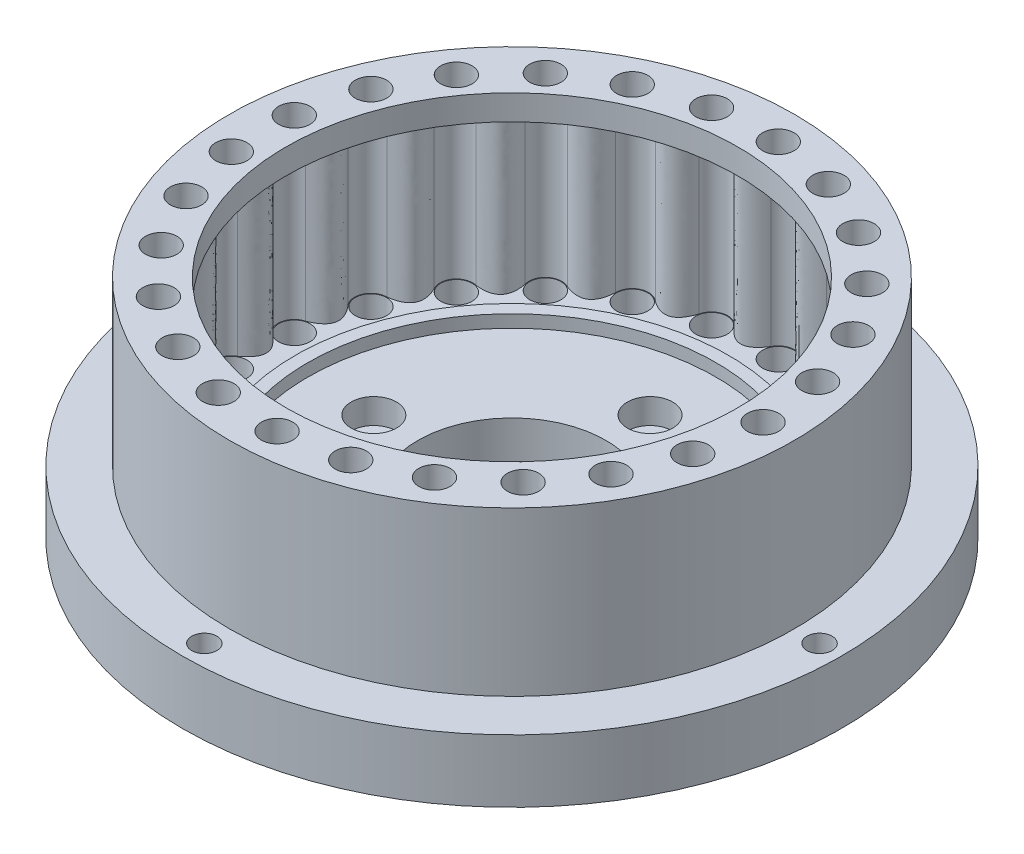
SolidWorks part; units mm, degrees
ref_plane "Front Plane" through (0, 0, 0) normal (0, 0, 1) x (1, 0, 0)
ref_plane "Top Plane" through (0, 0, 0) normal (0, 1, 0) x (1, 0, 0)
ref_plane "Right Plane" through (0, 0, 0) normal (1, 0, 0) x (0, 0, -1)
sketch "Sketch1" plane through (0, 0, 0) normal (0, 1, 0) x (1, 0, 0)
  circle A1 centre (0, 0) radius 45
  circle A2 centre (0, 0) radius 22 construction
  circle A3 centre (0, -22) radius 2
  circle A5 centre (-22, 0) radius 2
  circle A6 centre (0, 22) radius 2
  circle A7 centre (22, 0) radius 2
  point P15 (0, 0)
  dimension "D1" = 90
  dimension "D2" = 44
  dimension "D3" = 4
  dimension "D4" = 4
  dimension "D5" = 90
  dimension "D6" = 22
extrude "Boss-Extrude1" add sketch "Sketch1" along normal blind 6
sketch "Sketch2" plane through (0, 6, 0) normal (0, 1, 0) x (1, 0, 0)
  circle A0 centre (0, 0) radius 22 construction
  circle A1 centre (0, 22) radius 3.61
  circle A2 centre (22, 0) radius 3.61
  circle A3 centre (0, -22) radius 3.61
  circle A4 centre (-22, 0) radius 3.61
  point P14 (0, 0)
  dimension "D1" = 44
  dimension "D2" = 7.22
  dimension "D4" = 22
  dimension "D5" = 90
  dimension "D3" = 4
extrude "Cut-Extrude1" cut sketch "Sketch2" against normal blind 4
sketch "Sketch4" plane through (0, 6, 0) normal (0, 1, 0) x (1, 0, 0)
  circle A0 centre (0, 0) radius 15
  dimension "D1" = 30
extrude "Cut-Extrude2" cut sketch "Sketch4" against normal through all
sketch "Sketch5" plane through (0, 6, 0) normal (0, 1, 0) x (1, 0, 0)
  circle A0 centre (40, 0) radius 2.5
  circle A1 centre (38.7433, -9.9476) radius 2.5
  circle A2 centre (35.0523, -19.2701) radius 2.5
  circle A3 centre (29.1587, -27.3819) radius 2.5
  circle A4 centre (21.4331, -33.7731) radius 2.5
  circle A5 centre (12.3607, -38.0423) radius 2.5
  circle A6 centre (2.5116, -39.9211) radius 2.5
  circle A7 centre (-7.4953, -39.2915) radius 2.5
  circle A8 centre (-17.0312, -36.1931) radius 2.5
  circle A9 centre (-25.497, -30.8205) radius 2.5
  circle A10 centre (-32.3607, -23.5114) radius 2.5
  circle A11 centre (-37.1911, -14.725) radius 2.5
  circle A12 centre (-39.6846, -5.0133) radius 2.5
  circle A13 centre (-39.6846, 5.0133) radius 2.5
  circle A14 centre (-37.1911, 14.725) radius 2.5
  circle A15 centre (-32.3607, 23.5114) radius 2.5
  circle A16 centre (-25.497, 30.8205) radius 2.5
  circle A17 centre (-17.0312, 36.1931) radius 2.5
  circle A18 centre (-7.4953, 39.2915) radius 2.5
  circle A19 centre (2.5116, 39.9211) radius 2.5
  circle A20 centre (12.3607, 38.0423) radius 2.5
  circle A21 centre (21.4331, 33.7731) radius 2.5
  circle A22 centre (29.1587, 27.3819) radius 2.5
  circle A23 centre (35.0523, 19.2701) radius 2.5
  circle A24 centre (38.7433, 9.9476) radius 2.5
  point P53 (0, 0)
  dimension "D2" = 5
  dimension "D1" = 40
  dimension "D3" = 25
extrude "Cut-Extrude3" cut sketch "Sketch5" against normal blind 4
sketch "Sketch6" plane through (0, 6, 0) normal (0, 1, 0) x (1, 0, 0)
  circle A0 centre (0, 0) radius 32.5
  circle A1 centre (0, 0) radius 34.5
  dimension "D1" = 65
  dimension "D2" = 69
extrude "Boss-Extrude2" add sketch "Sketch6" along normal blind 2
sketch "Sketch7" plane through (0, 6, 0) normal (0, 1, 0) x (1, 0, 0)
  line L0 (0, 0) -> (35.0523, -19.2701) construction
  line L1 (0, 0) -> (27.3363, -25.6705) construction
  line L2 (35.0523, -19.2701) -> (34.7909, -21.7565) construction
  line L3 (29.1587, -27.3819) -> (31.4426, -26.365) construction
  line L4 (0, 0) -> (31.5517, -22.9236) construction
  circle A0 centre (35.0523, -19.2701) radius 2.5 construction
  circle A1 centre (38.7433, -9.9476) radius 2.5 construction
  circle A2 centre (40, 0) radius 2.5 construction
  circle A3 centre (38.7433, 9.9476) radius 2.5 construction
  circle A4 centre (35.0523, 19.2701) radius 2.5 construction
  circle A5 centre (29.1587, 27.3819) radius 2.5 construction
  circle A6 centre (21.4331, 33.7731) radius 2.5 construction
  circle A7 centre (12.3607, 38.0423) radius 2.5 construction
  circle A8 centre (2.5116, 39.9211) radius 2.5 construction
  circle A9 centre (-7.4953, 39.2915) radius 2.5 construction
  circle A10 centre (-17.0312, 36.1931) radius 2.5 construction
  circle A11 centre (-25.497, 30.8205) radius 2.5 construction
  circle A12 centre (-32.3607, 23.5114) radius 2.5 construction
  circle A13 centre (-37.1911, 14.725) radius 2.5 construction
  circle A14 centre (-39.6846, 5.0133) radius 2.5 construction
  circle A15 centre (-39.6846, -5.0133) radius 2.5 construction
  circle A16 centre (-37.1911, -14.725) radius 2.5 construction
  circle A17 centre (-32.3607, -23.5114) radius 2.5 construction
  circle A18 centre (-25.497, -30.8205) radius 2.5 construction
  circle A19 centre (-17.0312, -36.1931) radius 2.5 construction
  circle A20 centre (-7.4953, -39.2915) radius 2.5 construction
  circle A21 centre (2.5116, -39.9211) radius 2.5 construction
  circle A22 centre (12.3607, -38.0423) radius 2.5 construction
  circle A23 centre (21.4331, -33.7731) radius 2.5 construction
  circle A24 centre (29.1587, -27.3819) radius 2.5 construction
  arc A25 (34.7909, -21.7565) -> (37.0115, -17.7173) centre (35.0523, -19.2701) ccw construction
  arc A26 (39.1085, -12.4208) -> (40.2548, -7.9563) centre (38.7433, -9.9476) ccw construction
  arc A27 (40.9688, -2.3047) -> (40.9688, 2.3047) centre (40, 0) ccw construction
  arc A28 (40.2548, 7.9563) -> (39.1085, 12.4208) centre (38.7433, 9.9476) ccw construction
  arc A29 (37.0115, 17.7173) -> (34.7909, 21.7565) centre (35.0523, 19.2701) ccw construction
  arc A30 (31.4426, 26.365) -> (28.2873, 29.7251) centre (29.1587, 27.3819) ccw construction
  arc A31 (23.8981, 33.3562) -> (20.0063, 35.826) centre (21.4331, 33.7731) ccw construction
  arc A32 (14.8519, 38.2515) -> (10.4682, 39.6758) centre (12.3607, 38.0423) ccw construction
  arc A33 (4.8726, 40.7432) -> (0.2723, 41.0327) centre (2.5116, 39.9211) ccw construction
  arc A34 (-5.4129, 40.675) -> (-9.9406, 39.8113) centre (-7.4953, 39.2915) ccw construction
  arc A35 (-15.3583, 38.0509) -> (-19.529, 36.0884) centre (-17.0312, 36.1931) ccw construction
  arc A36 (-24.3387, 33.036) -> (-27.8903, 30.098) centre (-25.497, 30.8205) ccw construction
  arc A37 (-31.7898, 25.9454) -> (-34.4991, 22.2163) centre (-32.3607, 23.5114) ccw construction
  arc A38 (-37.2434, 17.2244) -> (-38.9402, 12.9388) centre (-37.1911, 14.725) ccw construction
  arc A39 (-40.3569, 7.4212) -> (-40.9346, 2.8483) centre (-39.6846, 5.0133) ccw construction
  arc A40 (-40.9346, -2.8483) -> (-40.3569, -7.4212) centre (-39.6846, -5.0133) ccw construction
  arc A41 (-38.9402, -12.9388) -> (-37.2434, -17.2244) centre (-37.1911, -14.725) ccw construction
  arc A42 (-34.4991, -22.2163) -> (-31.7898, -25.9454) centre (-32.3607, -23.5114) ccw construction
  arc A43 (-27.8903, -30.098) -> (-24.3387, -33.036) centre (-25.497, -30.8205) ccw construction
  arc A44 (-19.529, -36.0884) -> (-15.3583, -38.0509) centre (-17.0312, -36.1931) ccw construction
  arc A45 (-9.9406, -39.8113) -> (-5.4129, -40.675) centre (-7.4953, -39.2915) ccw construction
  arc A46 (0.2723, -41.0327) -> (4.8726, -40.7432) centre (2.5116, -39.9211) ccw construction
  arc A47 (10.4682, -39.6758) -> (14.8519, -38.2515) centre (12.3607, -38.0423) ccw construction
  arc A48 (20.0063, -35.826) -> (23.8981, -33.3562) centre (21.4331, -33.7731) ccw construction
  arc A49 (28.2873, -29.7251) -> (31.4426, -26.365) centre (29.1587, -27.3819) ccw construction
  arc A51 (33.4936, -21.8672) -> (35.0523, -19.2701) centre (0, 0) ccw construction
  arc A53 (23.9272, -32.0545) -> (27.0032, -29.5098) centre (0, 0) ccw construction
  arc A54 (15.2038, -36.9979) -> (18.8161, -35.2981) centre (0, 0) ccw construction
  arc A55 (9.9601, -38.7401) -> (14.713, -37.1958) centre (0, 0) ccw construction
  arc A56 (5.5252, -39.6166) -> (9.4467, -38.8685) centre (0, 0) ccw construction
  arc A57 (-5.0261, -39.683) -> (5.0006, -39.6862) centre (0, 0) ccw construction
  arc A58 (-14.7369, -37.1863) -> (-10.4469, -38.6117) centre (0, 0) ccw construction
  arc A59 (-23.0917, -32.6615) -> (-22.9047, -32.7929) centre (0, 0) ccw construction
  arc A60 (-30.4888, -25.8927) -> (-27.756, -28.8029) centre (0, 0) ccw construction
  arc A61 (-35.9702, -17.4969) -> (-34.047, -20.9953) centre (0, 0) ccw construction
  arc A62 (-39.1915, -8.0018) -> (-38.1986, -11.8686) centre (0, 0) ccw construction
  arc A63 (-39.9502, 1.9961) -> (-39.9502, -1.9961) centre (0, 0) ccw construction
  arc A64 (-38.1986, 11.8686) -> (-39.1915, 8.0018) centre (0, 0) ccw construction
  arc A65 (-36.1986, 17.0195) -> (-38.0383, 12.3729) centre (0, 0) ccw construction
  arc A66 (-34.047, 20.9953) -> (-35.9702, 17.4969) centre (0, 0) ccw construction
  arc A67 (-27.756, 28.8029) -> (-30.4888, 25.8927) centre (0, 0) ccw construction
  arc A68 (-19.2589, 35.0585) -> (-23.0917, 32.6615) centre (0, 0) ccw construction
  arc A69 (-9.9351, 38.7465) -> (-14.7369, 37.1863) centre (0, 0) ccw construction
  arc A70 (-0.5163, 39.9967) -> (-5.0261, 39.683) centre (0, 0) ccw construction
  arc A71 (9.4467, 38.8685) -> (0.0129, 40) centre (0, 0) ccw construction
  arc A72 (18.8161, 35.2981) -> (15.2038, 36.9979) centre (0, 0) ccw construction
  arc A73 (27.0032, 29.5098) -> (23.9272, 32.0545) centre (0, 0) ccw construction
  arc A74 (33.4936, 21.8672) -> (30.8123, 25.5069) centre (0, 0) ccw construction
  arc A75 (37.8795, 12.8507) -> (36.4099, 16.5626) centre (0, 0) ccw construction
  arc A76 (39.8853, 3.0267) -> (39.2891, 7.5079) centre (0, 0) ccw construction
  arc A77 (39.385, -6.9875) -> (39.9219, -2.4988) centre (0, 0) ccw construction
  arc A78 (36.1876, -17.0428) -> (37.8795, -12.8507) centre (0, 0) ccw construction
  circle A79 centre (0, 0) radius 45
  arc A80 (34.7861, -21.8565) -> (37.0934, -17.6596) centre (35.0523, -19.2701) ccw
  arc A81 (39.1287, -12.5189) -> (40.3198, -7.88) centre (38.7433, -9.9476) ccw
  arc A82 (41.0127, -2.3947) -> (41.0127, 2.3947) centre (40, 0) ccw
  arc A83 (40.3198, 7.88) -> (39.1287, 12.5189) centre (38.7433, 9.9476) ccw
  arc A84 (37.0934, 17.6596) -> (34.7861, 21.8565) centre (35.0523, 19.2701) ccw
  arc A85 (31.5362, 26.3295) -> (28.2577, 29.8208) centre (29.1587, 27.3819) ccw
  arc A86 (23.9976, 33.3451) -> (19.9538, 35.9113) centre (21.4331, 33.7731) ccw
  arc A87 (14.9511, 38.2654) -> (10.3962, 39.7454) centre (12.3607, 38.0423) ccw
  arc A88 (4.9651, 40.7814) -> (0.1853, 41.0822) centre (2.5116, 39.9211) ccw
  arc A89 (-5.3328, 40.735) -> (-10.0373, 39.8376) centre (-7.4953, 39.2915) ccw
  arc A90 (-15.2956, 38.129) -> (-19.6291, 36.0898) centre (-17.0312, 36.1931) ccw
  arc A91 (-24.2974, 33.1273) -> (-27.9876, 30.0744) centre (-25.497, 30.8205) ccw
  arc A92 (-31.7724, 26.044) -> (-34.5875, 22.1694) centre (-32.3607, 23.5114) ccw
  arc A93 (-37.2511, 17.3243) -> (-39.0142, 12.8713) centre (-37.1911, 14.725) ccw
  arc A94 (-40.3892, 7.516) -> (-40.9895, 2.7645) centre (-39.6846, 5.0133) ccw
  arc A95 (-40.9895, -2.7645) -> (-40.3892, -7.516) centre (-39.6846, -5.0133) ccw
  arc A96 (-39.0142, -12.8713) -> (-37.2511, -17.3243) centre (-37.1911, -14.725) ccw
  arc A97 (-34.5875, -22.1694) -> (-31.7724, -26.044) centre (-32.3607, -23.5114) ccw
  arc A98 (-27.9876, -30.0744) -> (-24.2974, -33.1273) centre (-25.497, -30.8205) ccw
  arc A99 (-19.6291, -36.0898) -> (-15.2956, -38.129) centre (-17.0312, -36.1931) ccw
  arc A100 (-10.0373, -39.8376) -> (-5.3328, -40.735) centre (-7.4953, -39.2915) ccw
  arc A101 (0.1853, -41.0822) -> (4.9651, -40.7814) centre (2.5116, -39.9211) ccw
  arc A102 (10.3962, -39.7454) -> (14.9511, -38.2654) centre (12.3607, -38.0423) ccw
  arc A103 (19.9538, -35.9113) -> (23.9976, -33.3451) centre (21.4331, -33.7731) ccw
  arc A104 (28.2577, -29.8208) -> (31.5362, -26.3295) centre (29.1587, -27.3819) ccw
  spline S0 degree 2 poles (34.7909, -21.7565) (29.9865, -21.7865) (31.4426, -26.365) knots 0 0 0 1 1 1 construction
  spline S1 degree 2 poles (28.2873, -29.7251) (23.6264, -28.5594) (23.8981, -33.3562) knots 0 0 0 1 1 1 construction
  spline S2 degree 2 poles (20.0063, -35.826) (15.7817, -33.5378) (14.8519, -38.2515) knots 0 0 0 1 1 1 construction
  spline S3 degree 2 poles (10.4682, -39.6758) (6.9454, -36.4089) (4.8726, -40.7432) knots 0 0 0 1 1 1 construction
  spline S4 degree 2 poles (0.2723, -41.0327) (-2.3274, -36.9923) (-5.4129, -40.675) knots 0 0 0 1 1 1 construction
  spline S5 degree 2 poles (-9.9406, -39.8113) (-11.4538, -35.2513) (-15.3583, -38.0509) knots 0 0 0 1 1 1 construction
  spline S6 degree 2 poles (-19.529, -36.0884) (-19.8606, -31.2954) (-24.3387, -33.036) knots 0 0 0 1 1 1 construction
  spline S7 degree 2 poles (-27.8903, -30.098) (-27.0195, -25.373) (-31.7898, -25.9454) knots 0 0 0 1 1 1 construction
  spline S8 degree 2 poles (-34.4991, -22.2163) (-32.4807, -17.8564) (-37.2434, -17.2244) knots 0 0 0 1 1 1 construction
  spline S9 degree 2 poles (-38.9402, -12.9388) (-35.9009, -9.2178) (-40.3569, -7.4212) knots 0 0 0 1 1 1 construction
  spline S10 degree 2 poles (-40.9346, -2.8483) (-37.0654, 0) (-40.9346, 2.8483) knots 0 0 0 1 1 1 construction
  spline S11 degree 2 poles (-40.3569, 7.4212) (-35.9009, 9.2178) (-38.9402, 12.9388) knots 0 0 0 1 1 1 construction
  spline S12 degree 2 poles (-37.2434, 17.2244) (-32.4807, 17.8564) (-34.4991, 22.2163) knots 0 0 0 1 1 1 construction
  spline S13 degree 2 poles (-31.7898, 25.9454) (-27.0195, 25.373) (-27.8903, 30.098) knots 0 0 0 1 1 1 construction
  spline S14 degree 2 poles (-24.3387, 33.036) (-19.8606, 31.2954) (-19.529, 36.0884) knots 0 0 0 1 1 1 construction
  spline S15 degree 2 poles (-15.3583, 38.0509) (-11.4538, 35.2513) (-9.9406, 39.8113) knots 0 0 0 1 1 1 construction
  spline S16 degree 2 poles (-5.4129, 40.675) (-2.3274, 36.9923) (0.2723, 41.0327) knots 0 0 0 1 1 1 construction
  spline S17 degree 2 poles (4.8726, 40.7432) (6.9454, 36.4089) (10.4682, 39.6758) knots 0 0 0 1 1 1 construction
  spline S18 degree 2 poles (14.8519, 38.2515) (15.7817, 33.5378) (20.0063, 35.826) knots 0 0 0 1 1 1 construction
  spline S19 degree 2 poles (23.8981, 33.3562) (23.6264, 28.5594) (28.2873, 29.7251) knots 0 0 0 1 1 1 construction
  spline S20 degree 2 poles (31.4426, 26.365) (29.9865, 21.7865) (34.7909, 21.7565) knots 0 0 0 1 1 1 construction
  spline S21 degree 2 poles (37.0115, 17.7173) (34.4625, 13.6447) (39.1085, 12.4208) knots 0 0 0 1 1 1 construction
  spline S22 degree 2 poles (40.2548, 7.9563) (36.7731, 4.6455) (40.9688, 2.3047) knots 0 0 0 1 1 1 construction
  spline S23 degree 2 poles (40.9688, -2.3047) (36.7731, -4.6455) (40.2548, -7.9563) knots 0 0 0 1 1 1 construction
  spline S24 degree 2 poles (39.1085, -12.4208) (34.4625, -13.6447) (37.0115, -17.7173) knots 0 0 0 1 1 1 construction
  spline S25 degree 1 poles (39.1287, -12.5189) (37.0934, -17.6596) knots 0 0 1 1 construction
  spline S26 degree 1 poles (41.0127, -2.3947) (40.3198, -7.88) knots 0 0 1 1 construction
  spline S27 degree 1 poles (40.3198, 7.88) (41.0127, 2.3947) knots 0 0 1 1 construction
  spline S28 degree 1 poles (37.0934, 17.6596) (39.1287, 12.5189) knots 0 0 1 1 construction
  spline S29 degree 1 poles (31.5362, 26.3295) (34.7861, 21.8565) knots 0 0 1 1 construction
  spline S30 degree 1 poles (23.9976, 33.3451) (28.2577, 29.8208) knots 0 0 1 1 construction
  spline S31 degree 1 poles (14.9511, 38.2654) (19.9538, 35.9113) knots 0 0 1 1 construction
  spline S32 degree 1 poles (4.9651, 40.7814) (10.3962, 39.7454) knots 0 0 1 1 construction
  spline S33 degree 1 poles (-5.3328, 40.735) (0.1853, 41.0822) knots 0 0 1 1 construction
  spline S34 degree 1 poles (-15.2956, 38.129) (-10.0373, 39.8376) knots 0 0 1 1 construction
  spline S35 degree 1 poles (-24.2974, 33.1273) (-19.6291, 36.0898) knots 0 0 1 1 construction
  spline S36 degree 1 poles (-31.7724, 26.044) (-27.9876, 30.0744) knots 0 0 1 1 construction
  spline S37 degree 1 poles (-37.2511, 17.3243) (-34.5875, 22.1694) knots 0 0 1 1 construction
  spline S38 degree 1 poles (-40.3892, 7.516) (-39.0142, 12.8713) knots 0 0 1 1 construction
  spline S39 degree 1 poles (-40.9895, -2.7645) (-40.9895, 2.7645) knots 0 0 1 1 construction
  spline S40 degree 1 poles (-39.0142, -12.8713) (-40.3892, -7.516) knots 0 0 1 1 construction
  spline S41 degree 1 poles (-34.5875, -22.1694) (-37.2511, -17.3243) knots 0 0 1 1 construction
  spline S42 degree 1 poles (-27.9876, -30.0744) (-31.7724, -26.044) knots 0 0 1 1 construction
  spline S43 degree 1 poles (-19.6291, -36.0898) (-24.2974, -33.1273) knots 0 0 1 1 construction
  spline S44 degree 1 poles (-10.0373, -39.8376) (-15.2956, -38.129) knots 0 0 1 1 construction
  spline S45 degree 1 poles (0.1853, -41.0822) (-5.3328, -40.735) knots 0 0 1 1 construction
  spline S46 degree 1 poles (10.3962, -39.7454) (4.9651, -40.7814) knots 0 0 1 1 construction
  spline S47 degree 1 poles (19.9538, -35.9113) (14.9511, -38.2654) knots 0 0 1 1 construction
  spline S48 degree 1 poles (28.2577, -29.8208) (23.9976, -33.3451) knots 0 0 1 1 construction
  spline S49 degree 1 poles (34.7861, -21.8565) (31.5362, -26.3295) knots 0 0 1 1 construction
  spline S50 degree 3 poles (37.0934, -17.6596) (36.9928, -17.4988) (36.7956, -17.161) (36.4917, -16.5417) (36.2467, -15.8185) (36.1759, -15.0518) (36.3187, -14.3796) (36.6748, -13.7918) (37.2512, -13.2814) (37.9249, -12.9219) (38.5703, -12.6785) (38.9453, -12.5673) (39.1287, -12.5189) knots 0.000577 0.000577 0.000577 0.000577 0.063005 0.125433 0.250288 0.375144 0.5 0.624856 0.749712 0.874567 0.936995 0.999423 0.999423 0.999423 0.999423
  spline S51 degree 3 poles (40.3198, -7.88) (40.1824, -7.7493) (39.9074, -7.4711) (39.459, -6.9469) (39.0418, -6.3073) (38.7826, -5.5824) (38.7538, -4.8957) (38.9524, -4.2379) (39.3838, -3.6001) (39.947, -3.0844) (40.5116, -2.6882) (40.8472, -2.4872) (41.0127, -2.3947) knots 0.000577 0.000577 0.000577 0.000577 0.063005 0.125433 0.250288 0.375144 0.5 0.624856 0.749712 0.874567 0.936995 0.999423 0.999423 0.999423 0.999423
  spline S52 degree 3 poles (41.0127, 2.3947) (40.8472, 2.4872) (40.5116, 2.6882) (39.947, 3.0844) (39.3838, 3.6001) (38.9524, 4.2379) (38.7538, 4.8957) (38.7826, 5.5824) (39.0418, 6.3073) (39.459, 6.9469) (39.9074, 7.4711) (40.1824, 7.7493) (40.3198, 7.88) knots 0.000577 0.000577 0.000577 0.000577 0.063005 0.125433 0.250288 0.375144 0.5 0.624856 0.749712 0.874567 0.936995 0.999423 0.999423 0.999423 0.999423
  spline S53 degree 3 poles (39.1287, 12.5189) (38.9453, 12.5673) (38.5703, 12.6785) (37.9249, 12.9219) (37.2512, 13.2814) (36.6748, 13.7918) (36.3187, 14.3796) (36.1759, 15.0518) (36.2467, 15.8185) (36.4917, 16.5417) (36.7956, 17.161) (36.9928, 17.4988) (37.0934, 17.6596) knots 0.000577 0.000577 0.000577 0.000577 0.063005 0.125433 0.250288 0.375144 0.5 0.624856 0.749712 0.874567 0.936995 0.999423 0.999423 0.999423 0.999423
  spline S54 degree 3 poles (34.7861, 21.8565) (34.5964, 21.8578) (34.2055, 21.8722) (33.5199, 21.9475) (32.7779, 22.1281) (32.0927, 22.4791) (31.6016, 22.9599) (31.2961, 23.5755) (31.174, 24.3357) (31.2315, 25.0971) (31.3718, 25.7725) (31.4789, 26.1488) (31.5362, 26.3295) knots 0.000577 0.000577 0.000577 0.000577 0.063005 0.125433 0.250288 0.375144 0.5 0.624856 0.749712 0.874567 0.936995 0.999423 0.999423 0.999423 0.999423
  spline S55 degree 3 poles (28.2577, 29.8208) (28.0737, 29.7749) (27.6915, 29.6917) (27.0087, 29.594) (26.2451, 29.5845) (25.4941, 29.754) (24.8989, 30.0976) (24.4499, 30.6179) (24.1426, 31.3238) (24.0089, 32.0756) (23.9769, 32.7647) (23.987, 33.1557) (23.9976, 33.3451) knots 0.000577 0.000577 0.000577 0.000577 0.063005 0.125433 0.250288 0.375144 0.5 0.624856 0.749712 0.874567 0.936995 0.999423 0.999423 0.999423 0.999423
  spline S56 degree 3 poles (19.9538, 35.9113) (19.787, 35.8211) (19.4375, 35.6454) (18.8004, 35.3811) (18.0632, 35.1819) (17.2936, 35.1594) (16.6317, 35.3442) (16.0674, 35.7364) (15.5942, 36.3437) (15.2777, 37.0387) (15.0754, 37.6981) (14.9879, 38.0794) (14.9511, 38.2654) knots 0.000577 0.000577 0.000577 0.000577 0.063005 0.125433 0.250288 0.375144 0.5 0.624856 0.749712 0.874567 0.936995 0.999423 0.999423 0.999423 0.999423
  spline S57 degree 3 poles (10.3962, 39.7454) (10.257, 39.6165) (9.9622, 39.3595) (9.4108, 38.945) (8.7463, 38.5687) (8.0065, 38.3555) (7.3194, 38.3699) (6.6753, 38.6095) (6.0659, 39.08) (5.5866, 39.6745) (5.2266, 40.2629) (5.0471, 40.6104) (4.9651, 40.7814) knots 0.000577 0.000577 0.000577 0.000577 0.063005 0.125433 0.250288 0.375144 0.5 0.624856 0.749712 0.874567 0.936995 0.999423 0.999423 0.999423 0.999423
  spline S58 degree 3 poles (0.1853, 41.0822) (0.0826, 40.9227) (-0.1391, 40.6004) (-0.57, 40.0618) (-1.1201, 39.5321) (-1.7837, 39.1417) (-2.4527, 38.9847) (-3.1362, 39.0566) (-3.8434, 39.3608) (-4.4555, 39.8174) (-4.9506, 40.2977) (-5.2109, 40.5897) (-5.3328, 40.735) knots 0.000577 0.000577 0.000577 0.000577 0.063005 0.125433 0.250288 0.375144 0.5 0.624856 0.749712 0.874567 0.936995 0.999423 0.999423 0.999423 0.999423
  spline S59 degree 3 poles (-10.0373, 39.8376) (-10.0971, 39.6576) (-10.2317, 39.2903) (-10.5151, 38.6614) (-10.9161, 38.0116) (-11.4618, 37.4684) (-12.0708, 37.15) (-12.7506, 37.0496) (-13.5113, 37.1684) (-14.2177, 37.4584) (-14.8167, 37.8005) (-15.1414, 38.0186) (-15.2956, 38.129) knots 0.000577 0.000577 0.000577 0.000577 0.063005 0.125433 0.250288 0.375144 0.5 0.624856 0.749712 0.874567 0.936995 0.999423 0.999423 0.999423 0.999423
  spline S60 degree 3 poles (-19.6291, 36.0898) (-19.6423, 35.9006) (-19.6813, 35.5114) (-19.7995, 34.8318) (-20.0263, 34.1027) (-20.4197, 33.4408) (-20.9303, 32.981) (-21.5639, 32.7147) (-22.3302, 32.6406) (-23.0866, 32.7458) (-23.7518, 32.9282) (-24.1206, 33.0586) (-24.2974, 33.1273) knots 0.000577 0.000577 0.000577 0.000577 0.063005 0.125433 0.250288 0.375144 0.5 0.624856 0.749712 0.874567 0.936995 0.999423 0.999423 0.999423 0.999423
  spline S61 degree 3 poles (-27.9876, 30.0744) (-27.9533, 29.8879) (-27.8943, 29.5012) (-27.8397, 28.8136) (-27.8781, 28.0509) (-28.0945, 27.3121) (-28.4748, 26.7396) (-29.0222, 26.3242) (-29.7461, 26.0618) (-30.5048, 25.9756) (-31.1945, 25.9869) (-31.5841, 26.0215) (-31.7724, 26.044) knots 0.000577 0.000577 0.000577 0.000577 0.063005 0.125433 0.250288 0.375144 0.5 0.624856 0.749712 0.874567 0.936995 0.999423 0.999423 0.999423 0.999423
  spline S62 degree 3 poles (-34.5875, 22.1694) (-34.508, 21.9972) (-34.3546, 21.6373) (-34.1308, 20.9849) (-33.9783, 20.2367) (-34.0041, 19.4672) (-34.2301, 18.8182) (-34.657, 18.2796) (-35.2928, 17.8455) (-36.0063, 17.5733) (-36.6771, 17.4127) (-37.0631, 17.3493) (-37.2511, 17.3243) knots 0.000577 0.000577 0.000577 0.000577 0.063005 0.125433 0.250288 0.375144 0.5 0.624856 0.749712 0.874567 0.936995 0.999423 0.999423 0.999423 0.999423
  spline S63 degree 3 poles (-39.0142, 12.8713) (-38.8943, 12.7243) (-38.6563, 12.4139) (-38.2772, 11.8376) (-37.9434, 11.1508) (-37.7771, 10.3991) (-37.8346, 9.7143) (-38.1141, 9.0865) (-38.622, 8.5078) (-39.2454, 8.0668) (-39.8552, 7.7444) (-40.2133, 7.587) (-40.3892, 7.516) knots 0.000577 0.000577 0.000577 0.000577 0.063005 0.125433 0.250288 0.375144 0.5 0.624856 0.749712 0.874567 0.936995 0.999423 0.999423 0.999423 0.999423
  spline S64 degree 3 poles (-40.9895, 2.7645) (-40.8368, 2.652) (-40.5291, 2.4105) (-40.0186, 1.9466) (-39.5245, 1.3644) (-39.1764, 0.6776) (-39.0618, 0) (-39.1764, -0.6776) (-39.5245, -1.3644) (-40.0186, -1.9466) (-40.5291, -2.4105) (-40.8368, -2.652) (-40.9895, -2.7645) knots 0.000577 0.000577 0.000577 0.000577 0.063005 0.125433 0.250288 0.375144 0.5 0.624856 0.749712 0.874567 0.936995 0.999423 0.999423 0.999423 0.999423
  spline S65 degree 3 poles (-40.3892, -7.516) (-40.2133, -7.587) (-39.8552, -7.7444) (-39.2454, -8.0668) (-38.622, -8.5078) (-38.1141, -9.0865) (-37.8346, -9.7143) (-37.7771, -10.3991) (-37.9434, -11.1508) (-38.2772, -11.8376) (-38.6563, -12.4139) (-38.8943, -12.7243) (-39.0142, -12.8713) knots 0.000577 0.000577 0.000577 0.000577 0.063005 0.125433 0.250288 0.375144 0.5 0.624856 0.749712 0.874567 0.936995 0.999423 0.999423 0.999423 0.999423
  spline S66 degree 3 poles (-37.2511, -17.3243) (-37.0631, -17.3493) (-36.6771, -17.4127) (-36.0063, -17.5733) (-35.2928, -17.8455) (-34.657, -18.2796) (-34.2301, -18.8182) (-34.0041, -19.4672) (-33.9783, -20.2367) (-34.1308, -20.9849) (-34.3546, -21.6373) (-34.508, -21.9972) (-34.5875, -22.1694) knots 0.000577 0.000577 0.000577 0.000577 0.063005 0.125433 0.250288 0.375144 0.5 0.624856 0.749712 0.874567 0.936995 0.999423 0.999423 0.999423 0.999423
  spline S67 degree 3 poles (-31.7724, -26.044) (-31.5841, -26.0215) (-31.1945, -25.9869) (-30.5048, -25.9756) (-29.7461, -26.0618) (-29.0222, -26.3242) (-28.4748, -26.7396) (-28.0945, -27.3121) (-27.8781, -28.0509) (-27.8397, -28.8136) (-27.8943, -29.5012) (-27.9533, -29.8879) (-27.9876, -30.0744) knots 0.000577 0.000577 0.000577 0.000577 0.063005 0.125433 0.250288 0.375144 0.5 0.624856 0.749712 0.874567 0.936995 0.999423 0.999423 0.999423 0.999423
  spline S68 degree 3 poles (-24.2974, -33.1273) (-24.1206, -33.0586) (-23.7518, -32.9282) (-23.0866, -32.7458) (-22.3302, -32.6406) (-21.5639, -32.7147) (-20.9303, -32.981) (-20.4197, -33.4408) (-20.0263, -34.1027) (-19.7995, -34.8318) (-19.6813, -35.5114) (-19.6423, -35.9006) (-19.6291, -36.0898) knots 0.000577 0.000577 0.000577 0.000577 0.063005 0.125433 0.250288 0.375144 0.5 0.624856 0.749712 0.874567 0.936995 0.999423 0.999423 0.999423 0.999423
  spline S69 degree 3 poles (-15.2956, -38.129) (-15.1414, -38.0186) (-14.8167, -37.8005) (-14.2177, -37.4584) (-13.5113, -37.1684) (-12.7506, -37.0496) (-12.0708, -37.15) (-11.4618, -37.4684) (-10.9161, -38.0116) (-10.5151, -38.6614) (-10.2317, -39.2903) (-10.0971, -39.6576) (-10.0373, -39.8376) knots 0.000577 0.000577 0.000577 0.000577 0.063005 0.125433 0.250288 0.375144 0.5 0.624856 0.749712 0.874567 0.936995 0.999423 0.999423 0.999423 0.999423
  spline S70 degree 3 poles (-5.3328, -40.735) (-5.2109, -40.5897) (-4.9506, -40.2977) (-4.4555, -39.8174) (-3.8434, -39.3608) (-3.1362, -39.0566) (-2.4527, -38.9847) (-1.7837, -39.1417) (-1.1201, -39.5321) (-0.57, -40.0618) (-0.1391, -40.6004) (0.0826, -40.9227) (0.1853, -41.0822) knots 0.000577 0.000577 0.000577 0.000577 0.063005 0.125433 0.250288 0.375144 0.5 0.624856 0.749712 0.874567 0.936995 0.999423 0.999423 0.999423 0.999423
  spline S71 degree 3 poles (4.9651, -40.7814) (5.0471, -40.6104) (5.2266, -40.2629) (5.5866, -39.6745) (6.0659, -39.08) (6.6753, -38.6095) (7.3194, -38.3699) (8.0065, -38.3555) (8.7463, -38.5687) (9.4108, -38.945) (9.9622, -39.3595) (10.257, -39.6165) (10.3962, -39.7454) knots 0.000577 0.000577 0.000577 0.000577 0.063005 0.125433 0.250288 0.375144 0.5 0.624856 0.749712 0.874567 0.936995 0.999423 0.999423 0.999423 0.999423
  spline S72 degree 3 poles (14.9511, -38.2654) (14.9879, -38.0794) (15.0754, -37.6981) (15.2777, -37.0387) (15.5942, -36.3437) (16.0674, -35.7364) (16.6317, -35.3442) (17.2936, -35.1594) (18.0632, -35.1819) (18.8004, -35.3811) (19.4375, -35.6454) (19.787, -35.8211) (19.9538, -35.9113) knots 0.000577 0.000577 0.000577 0.000577 0.063005 0.125433 0.250288 0.375144 0.5 0.624856 0.749712 0.874567 0.936995 0.999423 0.999423 0.999423 0.999423
  spline S73 degree 3 poles (23.9976, -33.3451) (23.987, -33.1557) (23.9769, -32.7647) (24.0089, -32.0756) (24.1426, -31.3238) (24.4499, -30.6179) (24.8989, -30.0976) (25.4941, -29.754) (26.2451, -29.5845) (27.0087, -29.594) (27.6915, -29.6917) (28.0737, -29.7749) (28.2577, -29.8208) knots 0.000577 0.000577 0.000577 0.000577 0.063005 0.125433 0.250288 0.375144 0.5 0.624856 0.749712 0.874567 0.936995 0.999423 0.999423 0.999423 0.999423
  spline S74 degree 3 poles (31.5362, -26.3295) (31.4789, -26.1488) (31.3718, -25.7725) (31.2315, -25.0971) (31.174, -24.3357) (31.2961, -23.5755) (31.6016, -22.9599) (32.0927, -22.4791) (32.7779, -22.1281) (33.5199, -21.9475) (34.2055, -21.8722) (34.5964, -21.8578) (34.7861, -21.8565) knots 0.000577 0.000577 0.000577 0.000577 0.063005 0.125433 0.250288 0.375144 0.5 0.624856 0.749712 0.874567 0.936995 0.999423 0.999423 0.999423 0.999423
  point P158 (0, 0)
  dimension "D1" = 7.2
  dimension "D2" = 0.1
extrude "Boss-Extrude4" add sketch "Sketch7" along normal blind 30
sketch "Sketch8" plane through (0, 36, 0) normal (0, 1, 0) x (1, 0, 0)
  circle A0 centre (0, 0) radius 36
  circle A1 centre (0, 0) radius 45
  dimension "D1" = 72
extrude "Boss-Extrude5" add sketch "Sketch8" against normal blind 4
sketch "Sketch9" plane through (0, 36, 0) normal (0, 1, 0) x (1, 0, 0)
  circle A0 centre (-17.0312, 36.1931) radius 2.5 construction
  circle A1 centre (-7.4953, 39.2915) radius 2.5 construction
  circle A2 centre (12.3607, 38.0423) radius 2.5 construction
  circle A3 centre (21.4331, 33.7731) radius 2.5 construction
  circle A4 centre (29.1587, 27.3819) radius 2.5 construction
  circle A5 centre (35.0523, 19.2701) radius 2.5 construction
  circle A6 centre (38.7433, 9.9476) radius 2.5 construction
  circle A7 centre (40, 0) radius 2.5 construction
  circle A8 centre (38.7433, -9.9476) radius 2.5 construction
  circle A9 centre (35.0523, -19.2701) radius 2.5 construction
  circle A10 centre (29.1587, -27.3819) radius 2.5 construction
  circle A11 centre (-7.4953, -39.2915) radius 2.5 construction
  circle A12 centre (12.3607, -38.0423) radius 2.5 construction
  circle A13 centre (2.5116, 39.9211) radius 2.5 construction
  circle A14 centre (-25.497, 30.8205) radius 2.5 construction
  circle A15 centre (-32.3607, 23.5114) radius 2.5 construction
  circle A16 centre (-37.1911, 14.725) radius 2.5 construction
  circle A17 centre (-39.6846, 5.0133) radius 2.5 construction
  circle A18 centre (-39.6846, -5.0133) radius 2.5 construction
  circle A19 centre (-37.1911, -14.725) radius 2.5 construction
  circle A20 centre (-32.3607, -23.5114) radius 2.5 construction
  circle A21 centre (-25.497, -30.8205) radius 2.5 construction
  circle A22 centre (-17.0312, -36.1931) radius 2.5 construction
  circle A23 centre (2.5116, -39.9211) radius 2.5 construction
  circle A24 centre (21.4331, -33.7731) radius 2.5 construction
  circle A25 centre (-17.0312, 36.1931) radius 2.5
  circle A26 centre (-7.4953, 39.2915) radius 2.5
  circle A27 centre (12.3607, 38.0423) radius 2.5
  circle A28 centre (21.4331, 33.7731) radius 2.5
  circle A29 centre (29.1587, 27.3819) radius 2.5
  circle A30 centre (35.0523, 19.2701) radius 2.5
  circle A31 centre (38.7433, 9.9476) radius 2.5
  circle A32 centre (40, 0) radius 2.5
  circle A33 centre (38.7433, -9.9476) radius 2.5
  circle A34 centre (35.0523, -19.2701) radius 2.5
  circle A35 centre (29.1587, -27.3819) radius 2.5
  circle A36 centre (-7.4953, -39.2915) radius 2.5
  circle A37 centre (12.3607, -38.0423) radius 2.5
  circle A38 centre (2.5116, 39.9211) radius 2.5
  circle A39 centre (-25.497, 30.8205) radius 2.5
  circle A40 centre (-32.3607, 23.5114) radius 2.5
  circle A41 centre (-37.1911, 14.725) radius 2.5
  circle A42 centre (-39.6846, 5.0133) radius 2.5
  circle A43 centre (-39.6846, -5.0133) radius 2.5
  circle A44 centre (-37.1911, -14.725) radius 2.5
  circle A45 centre (-32.3607, -23.5114) radius 2.5
  circle A46 centre (-25.497, -30.8205) radius 2.5
  circle A47 centre (-17.0312, -36.1931) radius 2.5
  circle A48 centre (2.5116, -39.9211) radius 2.5
  circle A49 centre (21.4331, -33.7731) radius 2.5
extrude "Cut-Extrude4" cut sketch "Sketch9" against normal blind 4
sketch "Sketch10" plane through (0, 0, 0) normal (0, 1, 0) x (1, 0, 0)
  circle A0 centre (0, 0) radius 52.5
  circle A1 centre (0, 0) radius 45 construction
  circle A2 centre (0, 0) radius 45
  dimension "D1" = 105
extrude "Boss-Extrude6" add sketch "Sketch10" along normal blind 10
sketch "Sketch11" plane through (0, 10, 0) normal (0, 1, 0) x (1, 0, 0)
  circle A0 centre (0, 0) radius 49 construction
  circle A1 centre (-49, 0) radius 2
  circle A2 centre (0, 49) radius 2
  circle A3 centre (49, 0) radius 2
  circle A4 centre (0, -49) radius 2
  point P14 (0, 0)
  dimension "D1" = 98
  dimension "D2" = 4
extrude "Cut-Extrude5" cut sketch "Sketch11" against normal blind 10
